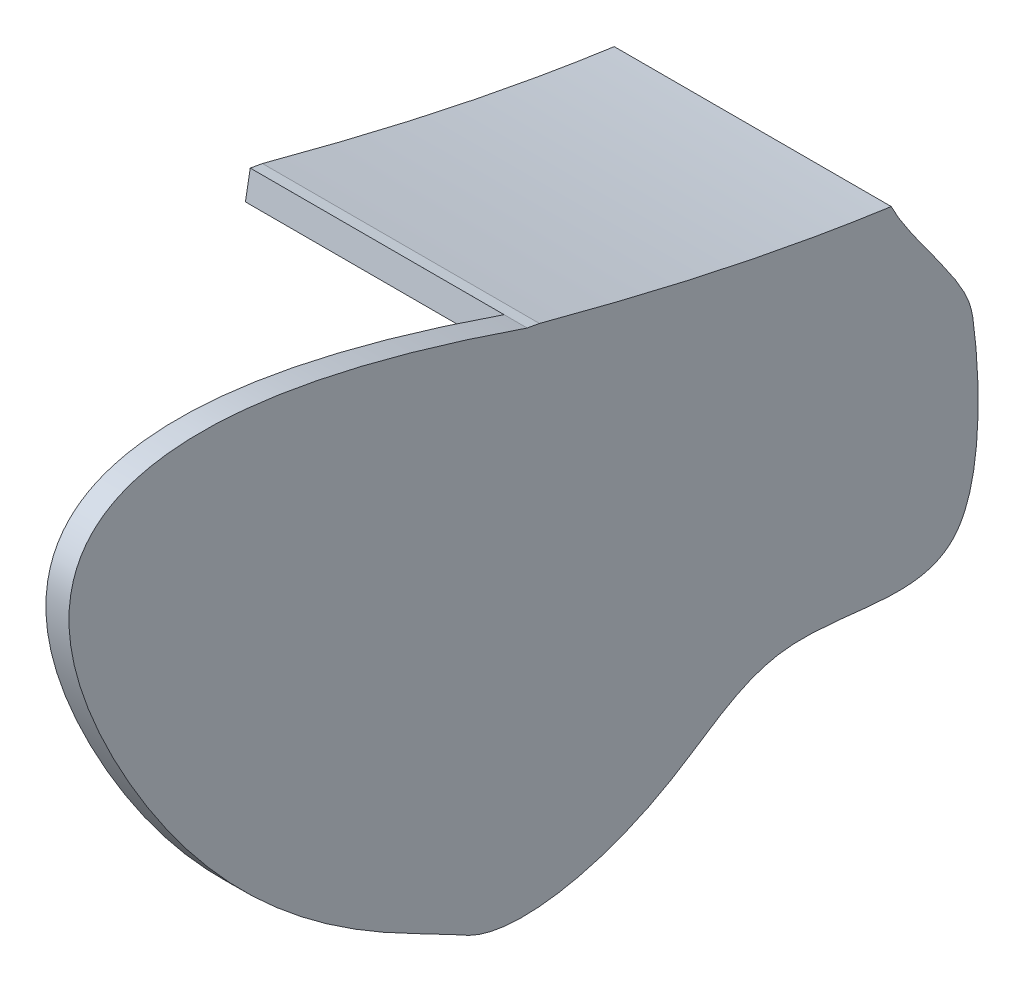
SolidWorks part; units mm, degrees
ref_plane "Front Plane" through (0, 0, 0) normal (0, 0, 1) x (1, 0, 0)
ref_plane "Top Plane" through (0, 0, 0) normal (0, 1, 0) x (1, 0, 0)
ref_plane "Right Plane" through (0, 0, 0) normal (1, 0, 0) x (0, 0, -1)
sketch "Sketch1" plane through (0, 0, 0) normal (0, 0, 1) x (1, 0, 0)
  line L1 (0, 80.3769) -> (-101.4897, 80.3769) construction
  line L2 (0, 80.3769) -> (0, -80.3769) construction
  line L3 (0, -80.3769) -> (-101.4897, -80.3769) construction
  line L4 (-101.4897, 80.3769) -> (-101.4897, -80.3769) construction
sketch "Sketch5" plane through (0, 0, 0) normal (1, 0, 0) x (0, 0, -1)
  line L1 (-77.0415, 38.4691) -> (4.7458, 38.4691)
  line L2 (-77.0415, 38.4691) -> (-77.0415, 95.3737)
  line L3 (-77.0415, 95.3737) -> (4.7458, 95.3737)
  line L4 (4.7458, 38.4691) -> (4.7458, 95.3737)
  point P4 (-76.6216, 38.4691)
extrude "Boss-Extrude4" add sketch "Sketch5" along normal blind 2.54
sketch "Sketch6" plane through (0, 0, 0) normal (-1, 0, 0) x (0, 0, 1)
  line L0 (5.7028, 81.1209) -> (13.8781, 82.3781)
  line L1 (13.8781, 82.3781) -> (22.1043, 83.9471)
  line L2 (22.1043, 83.9471) -> (31.2342, 85.9659)
  line L3 (31.2342, 85.9659) -> (43.961, 89.0919)
  line L4 (5.7028, 81.1209) -> (-19.7618, 75.625) construction
sketch "Sketch7" plane through (0, 0, 0) normal (0, 0, 1) x (1, 0, 0)
  line L2 (-11.4205, 79.8901) -> (0, 79.8901) construction
  point P0 (0, 79.8901)
  point P1 (0, 0)
ref_plane "Plane1" through (0, 77.4024, -13.8763) normal (0, -0.9843, 0.1765) x (-1, 0, 0)
sketch "Sketch8" plane through (0, 77.4024, -13.8763) normal (0, -0.9843, 0.1765) x (-1, 0, 0)
  line L0 (0, -82.6208) -> (0, -2.117) construction
  line L1 (27.94, -60.5537) -> (0, -60.5537)
  line L2 (27.94, -60.5537) -> (27.94, -19.63)
  line L3 (27.94, -19.63) -> (0, -19.63)
  line L4 (0, -60.5537) -> (0, -19.63)
  point P6 (0, 0)
  point P9 (27.94, -54.9225)
extrude "Boss-Extrude5" add sketch "Sketch8" against normal up to vertex (3.7254 mm away)
sketch "Sketch10" plane through (0, 0, 0) normal (1, 0, 0) x (0, 0, -1)
  line L6 (-40.2425, 96.3882) -> (-45.0494, 91.8666)
  line L7 (0.7505, 86.6579) -> (-40.2425, 96.3882)
  line L8 (-5.0095, 83.2992) -> (0.7505, 86.6579)
  spline S2 degree 3 poles (-45.0494, 91.8666) (-40.0252, 90.5238) (-26.8103, 87.1003) (-13.3673, 84.4717) (-5.0095, 83.2992) knots 0 0 0 0 0.3809 1 1 1 1
extrude "Cut-Extrude1" cut sketch "Sketch10" against normal through all both and the other way through all
sketch "Sketch11" plane through (-27.94, 0, 0) normal (-1, 0, 0) x (0, 0, 1)
  line L0 (9.5578, 82.4159) -> (5.7028, 81.1209) construction
  line L1 (53.4559, 90.6834) -> (30.6863, 63.9899)
  line L2 (30.6863, 63.9899) -> (2.2568, 78.8988)
  line L3 (2.2568, 78.8988) -> (3.8278, 81.664)
  line L4 (3.8278, 81.664) -> (5.7326, 81.1309)
  spline S0 degree 3 poles (5.7326, 81.1309) (24.1232, 83.8211) (37.0471, 86.6806) (53.4559, 90.6834) knots 0 0 0 0 1 1 1 1
extrude "Cut-Extrude2" cut sketch "Sketch11" against normal through all both and the other way through all
sketch "Sketch12" plane through (0, 11.799, -13.8324) normal (0, 0.649, -0.7608) x (-1, 0, 0)
  line L4 (0, 68.5989) -> (0, 103.6845)
  line L5 (0, 103.6845) -> (-2.54, 103.6845)
  line L6 (-2.54, 103.6845) -> (-2.54, 68.5989)
  line L7 (-2.54, 68.5989) -> (0, 68.5989)
  line L8 (0, 68.5989) -> (0, 103.6845)
  line L9 (0, 103.6845) -> (-2.54, 103.6845)
  line L10 (-2.54, 103.6845) -> (-2.54, 68.5989)
  line L11 (-2.54, 68.5989) -> (0, 68.5989)
  dimension "D1" = 0
extrude "Boss-Extrude6" add sketch "Sketch12" along normal up to next
sketch "Sketch13" plane through (0, 52.1909, 44.5187) normal (0, -0.7608, -0.649) x (1, 0, 0)
  line L4 (0, -45.5507) -> (2.54, -45.5507)
  line L5 (2.54, -45.5507) -> (2.54, -18.1811)
  line L6 (2.54, -18.1811) -> (0, -18.1811)
  line L7 (0, -18.1811) -> (0, -45.5507)
  line L8 (0, -45.5507) -> (2.54, -45.5507)
  line L9 (2.54, -45.5507) -> (2.54, -18.1811)
  line L10 (2.54, -18.1811) -> (0, -18.1811)
  line L11 (0, -18.1811) -> (0, -45.5507)
  dimension "D1" = 0
extrude "Boss-Extrude7" add sketch "Sketch13" along normal up to next
sketch "Sketch14" plane through (0, 82.2044, -19.5126) normal (0, -0.973, 0.2309) x (1, 0, 0)
  line L4 (0, 57.0225) -> (0, 19.2834)
  line L5 (0, 19.2834) -> (2.54, 19.2834)
  line L6 (2.54, 19.2834) -> (2.54, 57.0225)
  line L7 (2.54, 57.0225) -> (0, 57.0225)
  line L8 (0, 57.0225) -> (0, 19.2834)
  line L9 (0, 19.2834) -> (2.54, 19.2834)
  line L10 (2.54, 19.2834) -> (2.54, 57.0225)
  line L11 (2.54, 57.0225) -> (0, 57.0225)
  dimension "D1" = 0
extrude "Boss-Extrude8" add sketch "Sketch14" along normal up to next
sketch "Sketch15" plane through (0, 29.5611, -34.6555) normal (0, 0.649, -0.7608) x (-1, 0, 0)
  line L4 (-2.54, 62.3853) -> (0, 62.3853)
  line L5 (0, 62.3853) -> (0, 68.5989)
  line L6 (0, 68.5989) -> (-2.54, 68.5989)
  line L7 (-2.54, 68.5989) -> (-2.54, 62.3853)
  line L8 (-2.54, 62.3853) -> (0, 62.3853)
  line L9 (0, 62.3853) -> (0, 68.5989)
  line L10 (0, 68.5989) -> (-2.54, 68.5989)
  line L11 (-2.54, 68.5989) -> (-2.54, 62.3853)
  dimension "D1" = 0
extrude "Boss-Extrude9" add sketch "Sketch15" along normal up to next
sketch "Sketch16" plane through (0, 47.4635, 40.4863) normal (0, -0.7608, -0.649) x (1, 0, 0)
  line L4 (0, -49.6575) -> (2.54, -49.6575)
  line L5 (2.54, -49.6575) -> (2.54, -45.5507)
  line L6 (2.54, -45.5507) -> (0, -45.5507)
  line L7 (0, -45.5507) -> (0, -49.6575)
  line L8 (0, -49.6575) -> (2.54, -49.6575)
  line L9 (2.54, -49.6575) -> (2.54, -45.5507)
  line L10 (2.54, -45.5507) -> (0, -45.5507)
  line L11 (0, -45.5507) -> (0, -49.6575)
  dimension "D1" = 0
extrude "Boss-Extrude10" add sketch "Sketch16" along normal up to next
sketch "Sketch17" plane through (0, 0, 0) normal (-1, 0, 0) x (0, 0, 1)
  line L0 (45.0698, 91.7547) -> (45.668, 102.5657)
  line L1 (45.668, 102.5657) -> (-10.1696, 101.1945)
  line L2 (-10.1696, 101.1945) -> (-11.2974, 80.8111)
  line L3 (-11.2974, 80.8111) -> (5.0095, 83.2992)
  line L4 (37.2831, 89.835) -> (41.3488, 93.9007)
  line L5 (41.3488, 93.9007) -> (43.7249, 91.5136)
  line L6 (43.7249, 91.5136) -> (45.0698, 91.7547)
  spline S0 degree 3 poles (1418.3241, -2540.295) (340.6563, 308.0051) (42.2111, -85.7155) (-447.753, 188.0874) (97.7018, 3037.7559) knots -12.785248 -12.785248 -12.785248 -12.785248 0.3809 16.192892 16.192892 16.192892 16.192892 only from (37.2831, 89.835) to (5.0095, 83.2992) construction
  spline S1 degree 3 poles (37.2831, 89.835) (34.8364, 89.2124) (24.1755, 86.5851) (13.3673, 84.4717) (5.0095, 83.2992) knots 0.195994 0.195994 0.195994 0.195994 0.3809 1 1 1 1
extrude "Cut-Extrude4" cut sketch "Sketch17" against normal through all both and the other way through all
sketch "Sketch18" plane through (0, 0, 0) normal (-1, 0, 0) x (0, 0, 1)
  line L0 (47.5753, 38.4691) -> (45.8236, 95.3737)
  line L1 (77.0415, 38.4691) -> (-4.7458, 38.4691) construction
  line L2 (45.2701, 95.3737) -> (77.0415, 95.3737) construction
  line L3 (45.8236, 95.3737) -> (45.0457, 120.6429)
  line L4 (45.0457, 120.6429) -> (118.7902, 122.9129)
  line L5 (118.7902, 122.9129) -> (121.4931, 35.1067)
  line L6 (121.4931, 35.1067) -> (47.5753, 25.5839)
  line L7 (47.5753, 25.5839) -> (47.5753, 38.4691) construction
  line L9 (31.9144, 38.4691) -> (31.9144, 23.6291)
  line L10 (31.9144, 23.6291) -> (47.5753, 25.5839)
  line L11 (31.9144, 38.4691) -> (47.5753, 38.4691)
  point P12 (0, 0)
extrude "Boss-Extrude11" add sketch "Sketch18" against normal up to vertex (2.54 mm away)
sketch "Sketch20" plane through (0, 0, 0) normal (-1, 0, 0) x (0, 0, 1)
  line L0 (5.0095, 83.2992) -> (3.9664, 97.8629)
  line L1 (3.9664, 97.8629) -> (45.0699, 91.7546)
  line L2 (45.0698, 91.7547) -> (45.6002, 88.7963) construction
  line L3 (45.0698, 91.7547) -> (45.6002, 88.7963) construction
  spline S0 degree 3 poles (45.0699, 91.7546) (88.0667, 106.5985) (102.6989, 96.3525) (78.2342, 49.1154) (56.3388, 40.1338) (47.6394, 34.4594) (32.8726, 36.7827) (16.4186, 50.574) (-5.6004, 40.5346) (-4.6785, 63.6881) (-3.3621, 72.3368) (3.144, 79.3686) (5.0095, 83.2992) knots 0 0 0 0 0.141853 0.193045 0.364595 0.404896 0.596063 0.67876 0.810882 0.912493 0.931405 1 1 1 1
  point P2 (45.0776, 91.8949)
extrude "Cut-Extrude5" cut sketch "Sketch20" against normal through all both and the other way through all flip side to cut
